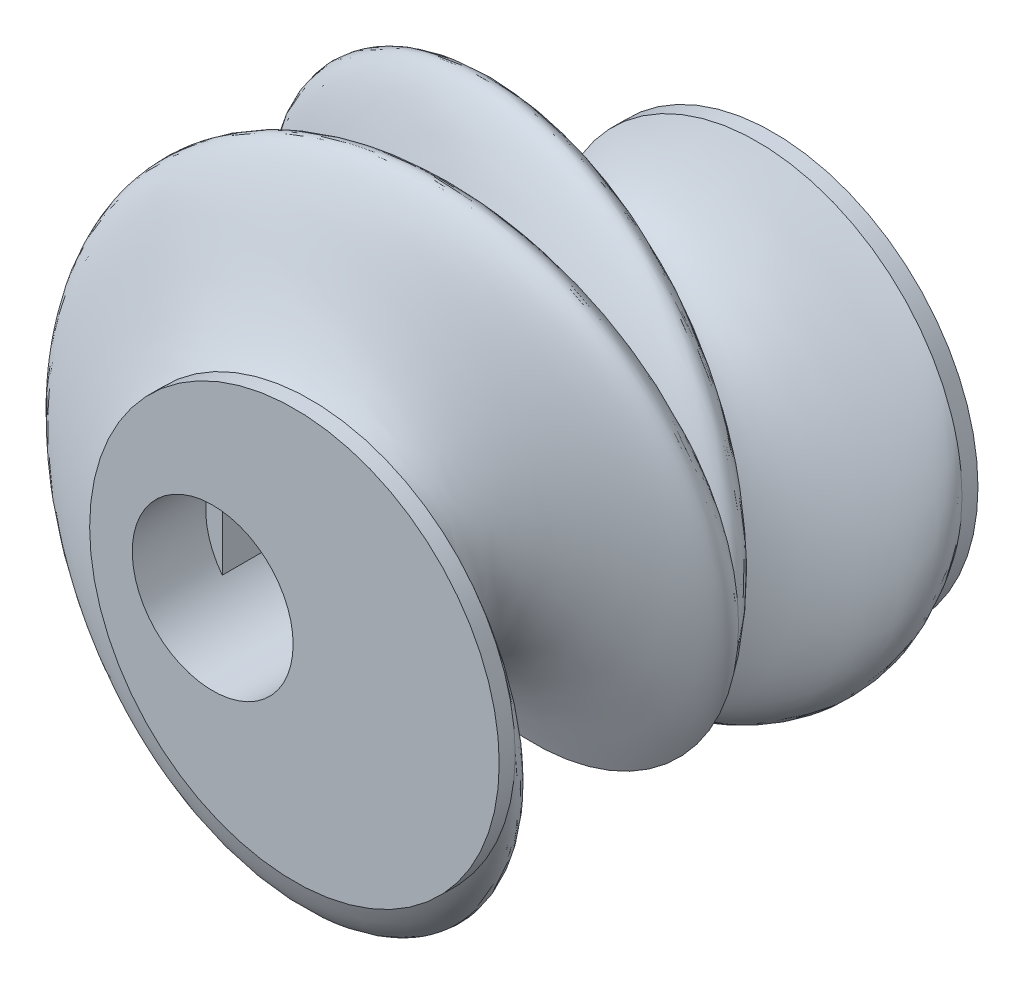
SolidWorks part; units mm, degrees
note: '?' marks a value the reader was unsure of.
ref_plane "Ebene vorne" through (0, 0, 0) normal (0, 0, 1) x (1, 0, 0)
ref_plane "Ebene oben" through (0, 0, 0) normal (0, 1, 0) x (1, 0, 0)
ref_plane "Ebene rechts" through (0, 0, 0) normal (1, 0, 0) x (0, 0, -1)
sketch "Skizze1" plane through (0, 0, 0) normal (0, 0, 1) x (1, 0, 0)
  circle A0 centre (0, 0) radius 6.4173
  dimension "D1" = 12.8346
ref_plane "Ebene1" through (0, 0, 0) normal (0, 0, 1) x (1, 0, 0)
sketch "Skizze3" plane through (0, 0, 0) normal (0, 0, 1) x (1, 0, 0)
  point P0 (-2.5613, 0)
  dimension "D1" = 2.5613
ref_axis "Achse1" through (-2.5613, 0, -26.4244) along (0, 0, 1)?
sketch "Skizze4" plane through (0, 0, 0) normal (0, 0, 1) x (1, 0, 0)
  circle A0 centre (-2.5613, 0) radius 3.5
  dimension "D1" = 7
curve "Spirale/Helix2" pitch 7 height 7 radius 3.5 centre (-2.5613, 0, 0) axis (0, 0, 1) start towards (1, 0, 0)
sweep "Austragung1" add profiles "Skizze1" path "Spirale/Helix2"
sketch "Skizze5" plane through (0, 0, 7) normal (0, 0, 1) x (1, 0, 0)
  circle A0 centre (-2.5613, 0) radius 2.5
extrude "Schnitt-Linear austragen1" cut sketch "Skizze5" against normal blind 10
sketch "Skizze6" plane through (0, 0, 0) normal (0, 0, -1) x (-1, 0, 0)
  circle A0 centre (0, 0) radius 6.4173
sketch "Skizze7" plane through (0, 0, 0) normal (0, 0, 1) x (1, 0, 0)
  circle A0 centre (-2.5613, 0) radius 3.5
  dimension "D1" = 7
curve "Spirale/Helix3" pitch 7 height 7 radius 3.5 left hand yes centre (-2.5613, 0, 0) axis (0, 0, -1) start towards (1, 0, 0)
sweep "Austragung2" add profiles "Skizze6" path "Spirale/Helix3"
sketch "Skizze8" plane through (0, 0, -7) normal (0, 0, -1) x (-1, 0, 0)
  circle A0 centre (2.5613, 0) radius 3.5
  dimension "D1" = 7
extrude "Aufsatz-Linear austragen1" add sketch "Skizze8" along normal blind 1.8
sketch "Skizze9" plane through (0, 0, -8.8) normal (0, 0, -1) x (-1, 0, 0)
  circle A0 centre (2.5613, 0) radius 2.6
extrude "Schnitt-Linear austragen2" cut sketch "Skizze9" against normal blind 5
sketch "Skizze11" plane through (0, 0, -3.8) normal (0, 0, -1) x (-1, 0, 0)
  line L0 (4.5613, -2.4134) -> (5.7613, 0)
  line L4 (4.5613, 2.4134) -> (4.5613, -2.4134)
  line L5 (5.3613, 0.8045) -> (4.5613, -2.4134) construction
  line L6 (5.3613, -0.8045) -> (4.5613, 2.4134) construction
  line L7 (5.7613, 0) -> (4.5613, 2.4134)
  circle A0 centre (2.5613, 0) radius 2.6 construction
  point P0 (5.1613, 0)
sketch "Skizze12" plane through (0, 0, -3.8) normal (0, 0, -1) x (-1, 0, 0)
  circle A0 centre (2.5613, 0) radius 2.52
extrude "Schnitt-Linear austragen4" cut sketch "Skizze12" against normal blind 36
extrude "Aufsatz-Linear austragen2" add sketch "Skizze11" against normal blind 9
sketch "Skizze13" plane through (0, 0, -7) normal (0, 0, -1) x (-1, 0, 0)
  circle A0 centre (0, 0) radius 6.4173
  circle A1 centre (2.5613, 0) radius 3.5
extrude "Aufsatz-Linear austragen3" add sketch "Skizze13" along normal blind 0.5
sketch "Skizze14" plane through (0, 0, 7) normal (0, 0, 1) x (1, 0, 0)
  circle A0 centre (0, 0) radius 6.4173
  circle A1 centre (-2.5613, 0) radius 2.52
extrude "Aufsatz-Linear austragen4" add sketch "Skizze14" along normal blind 0.5
